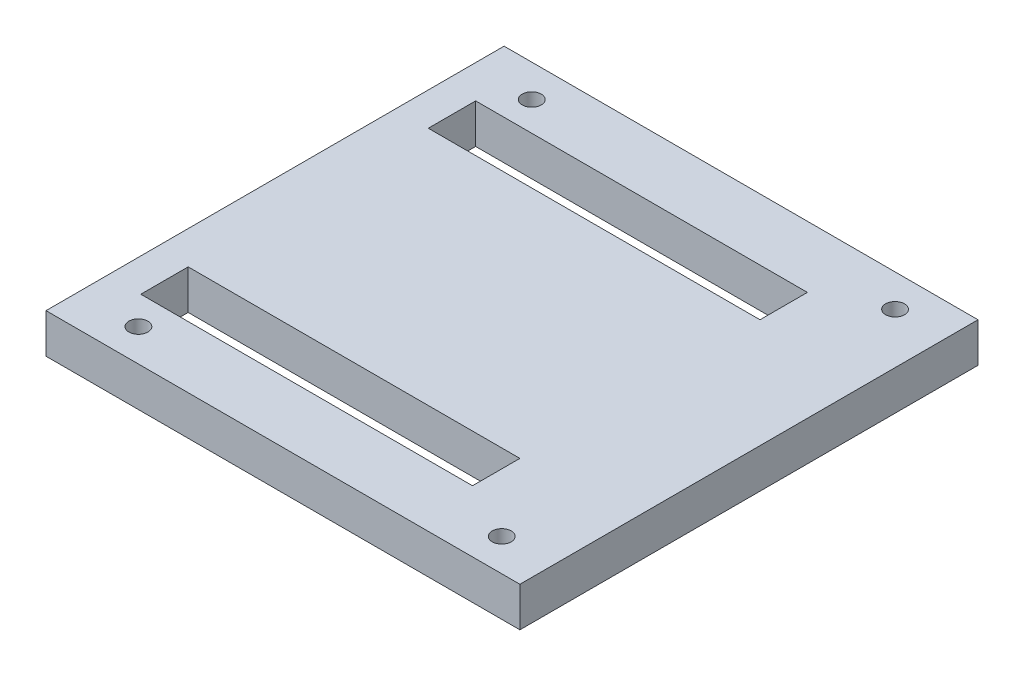
SolidWorks part; units mm, degrees
ref_plane "前视基准面" through (0, 0, 0) normal (0, 0, 1) x (1, 0, 0)
ref_plane "上视基准面" through (0, 0, 0) normal (0, 1, 0) x (1, 0, 0)
ref_plane "右视基准面" through (0, 0, 0) normal (1, 0, 0) x (0, 0, -1)
other "Configuration Table"
sketch "草图1" plane through (0, 0, 0) normal (0, 1, 0) x (1, 0, 0)
  line L0 (0, 7.6) -> (0, -7.6) construction
  line L1 (-15, -14.5) -> (15, -14.5)
  line L2 (-15, -14.5) -> (-15, 14.5)
  line L3 (-15, 14.5) -> (15, 14.5)
  line L4 (15, -14.5) -> (15, 14.5)
  line L5 (-15, -14.5) -> (15, 14.5) construction
  line L6 (-15, 14.5) -> (15, -14.5) construction
  line L7 (-12.9, 10.6) -> (8.1, 10.6)
  line L8 (-12.9, 10.6) -> (-12.9, 7.6)
  line L9 (-12.9, 7.6) -> (8.1, 7.6)
  line L10 (8.1, 10.6) -> (8.1, 7.6)
  line L11 (-12.9, -7.6) -> (8.1, -7.6)
  line L12 (-12.9, -7.6) -> (-12.9, -10.6)
  line L13 (-12.9, -10.6) -> (8.1, -10.6)
  line L14 (8.1, -7.6) -> (8.1, -10.6)
  point P0 (0, 0)
  point P7 (0, 0)
  dimension "D1" = 29
  dimension "D2" = 30
  dimension "D3" = 3
  dimension "D4" = 21
  dimension "D5" = 15.2
  dimension "D7" = 2.1
extrude "凸台-拉伸1" add sketch "草图1" along normal blind 2.5
sketch "草图2" plane through (0, 0, 0) normal (0, -1, 0) x (1, 0, 0)
  circle A0 centre (-11.2, -12.45) radius 1
  circle A1 centre (-11.2, -12.45) radius 0.6
  circle A2 centre (-11.2, 12.45) radius 1
  circle A3 centre (-11.2, 12.45) radius 0.6
  circle A4 centre (11.8, 12.45) radius 1
  circle A5 centre (11.8, 12.45) radius 0.6
  circle A6 centre (11.8, -12.45) radius 1
  circle A7 centre (11.8, -12.45) radius 0.6
  dimension "D1" = 1.2
  dimension "D2" = 2
extrude "切除-拉伸1" cut sketch "草图2" against normal through all contours A5 | A7 | A1 | A3
extrude "切除-拉伸2" cut sketch "草图2<3>" against normal blind 1.5
sketch "草图2<3>" plane through (0, 0, 0) normal (0, -1, 0) x (1, 0, 0) same geometry as "草图2"
